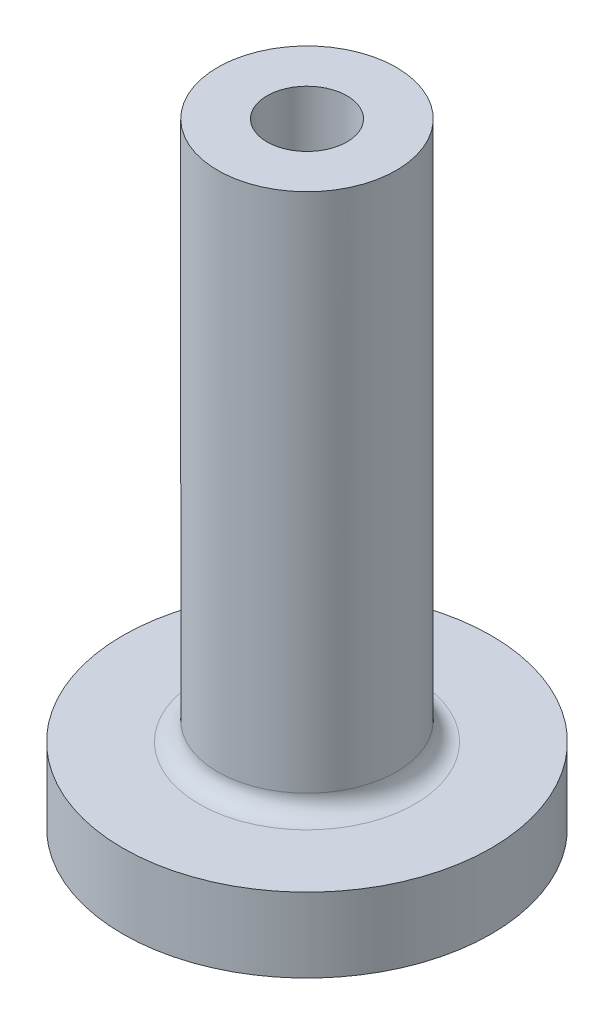
SolidWorks part; units mm, degrees
ref_plane "Front Plane" through (0, 0, 0) normal (0, 0, 1) x (1, 0, 0)
ref_plane "Top Plane" through (0, 0, 0) normal (0, 1, 0) x (1, 0, 0)
ref_plane "Right Plane" through (0, 0, 0) normal (1, 0, 0) x (0, 0, -1)
sketch "Sketch1" plane through (0, 0, 0) normal (0, 1, 0) x (1, 0, 0)
  circle A0 centre (0, 0) radius 9.9
  circle A1 centre (0, 0) radius 4.8
  circle A2 centre (0, 0) radius 2.15
  dimension "D1" = 4.3
  dimension "D2" = 9.6
  dimension "D3" = 19.8
extrude "Boss-Extrude1" add sketch "Sketch1" along normal blind 4 contours A2 | A1 A2 | A0 A1 region at (-9.62, 0, 0) region at (-4.6642, 0, 0) region at (0, 0, 0)
extrude "Boss-Extrude2" add sketch "Sketch1<3>" along normal blind 29 from surface contours A2 | A1 A2 region at (-4.6642, 0, 0) region at (0, 0, 0) starting at face at (0, 4, 9.9)
sketch "Sketch1<3>" plane through (0, 0, 0) normal (0, 1, 0) x (1, 0, 0) same geometry as "Sketch1"
extrude "Cut-Extrude1" cut sketch "Sketch1<4>" against normal blind 8 from surface contours A2 region at (0, 0, 0) starting at face at (0, 33, 4.8)
sketch "Sketch1<4>" plane through (0, 0, 0) normal (0, 1, 0) x (1, 0, 0) same geometry as "Sketch1"
fillet "Fillet1" radius 1 1 edges at (0, 4, 4.8)
